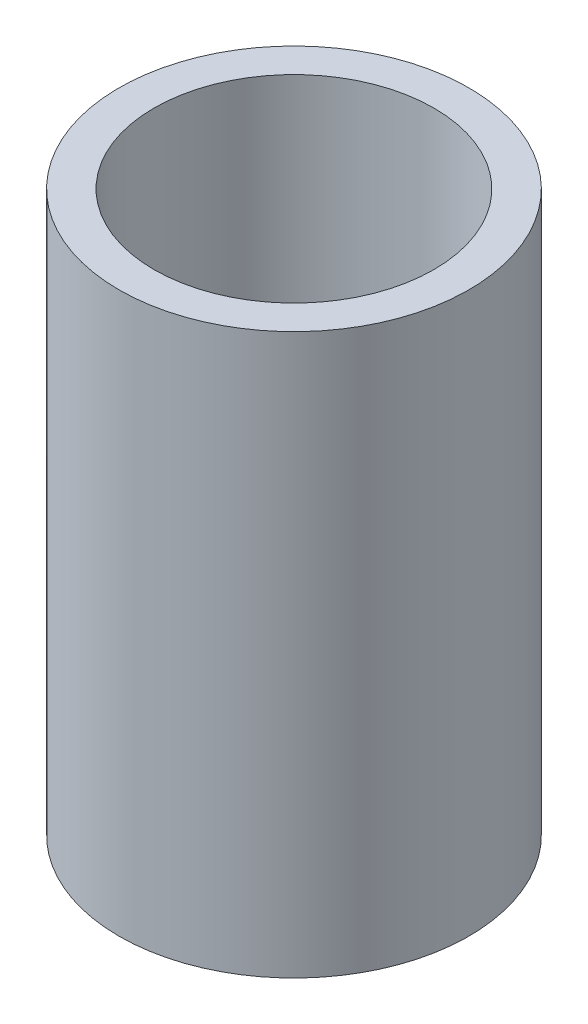
SolidWorks part; units mm, degrees
ref_plane "Front Plane" through (0, 0, 0) normal (0, 0, 1) x (1, 0, 0)
ref_plane "Top Plane" through (0, 0, 0) normal (0, 1, 0) x (1, 0, 0)
ref_plane "Right Plane" through (0, 0, 0) normal (1, 0, 0) x (0, 0, -1)
sketch "Sketch2" plane through (0, 0, 0) normal (0, 1, 0) x (1, 0, 0)
  circle A0 centre (0, 0) radius 50.8
  circle A1 centre (0, 0) radius 63.5
  dimension "D1" = 101.6
extrude "Boss-Extrude1" add sketch "Sketch2" along normal blind 203.2
